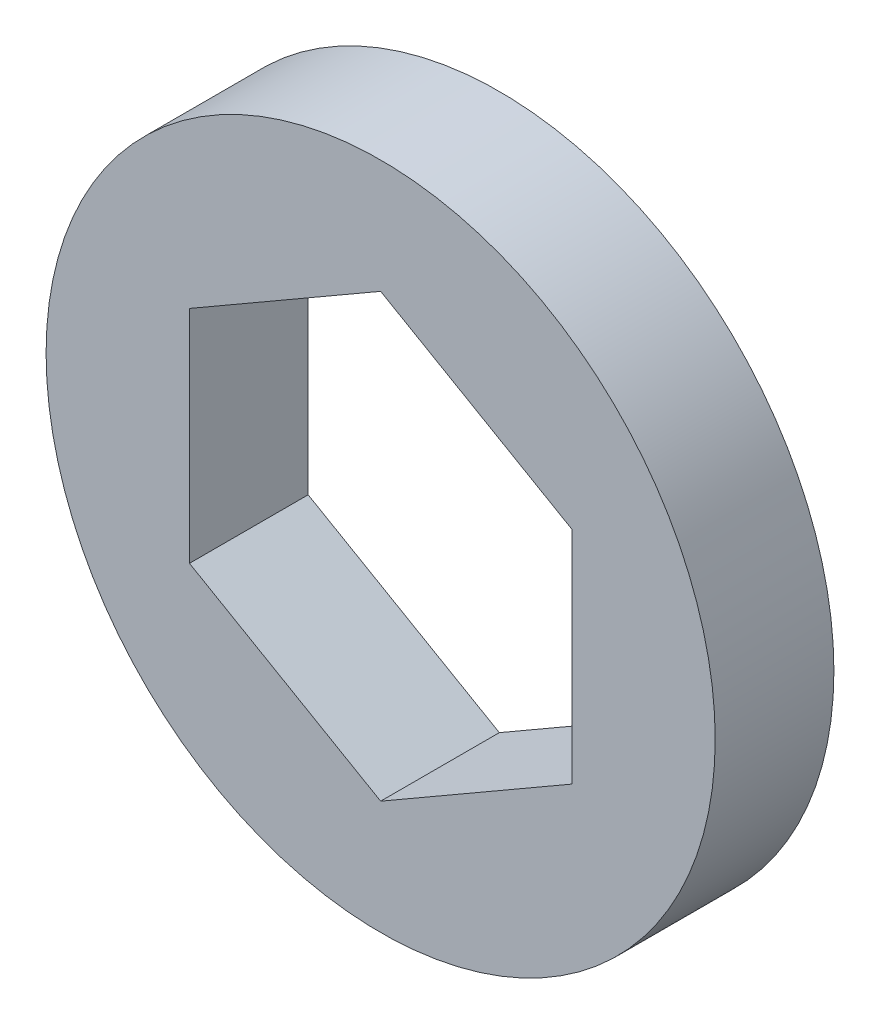
SolidWorks part; units mm, degrees
material "Nylon 101"
ref_plane "Front Plane" through (0, 0, 0) normal (0, 0, 1) x (1, 0, 0)
ref_plane "Top Plane" through (0, 0, 0) normal (0, 1, 0) x (1, 0, 0)
ref_plane "Right Plane" through (0, 0, 0) normal (1, 0, 0) x (0, 0, -1)
sketch "Sketch1" plane through (0, 0, 0) normal (0, 0, 1) x (1, 0, 0)
  line L1 (0, 7.3323) -> (-6.35, 3.6662)
  line L2 (-6.35, 3.6662) -> (-6.35, -3.6662)
  line L3 (-6.35, -3.6662) -> (0, -7.3323)
  line L4 (0, -7.3323) -> (6.35, -3.6662)
  line L5 (6.35, -3.6662) -> (6.35, 3.6662)
  line L6 (6.35, 3.6662) -> (0, 7.3323)
  circle A0 centre (0, 0) radius 11.1125
  circle A1 centre (0, 0) radius 6.35 construction
  dimension "D1" = 12.7
  dimension "D2" = 22.225
extrude "Boss-Extrude1" add sketch "Sketch1" along normal blind 3.9426
